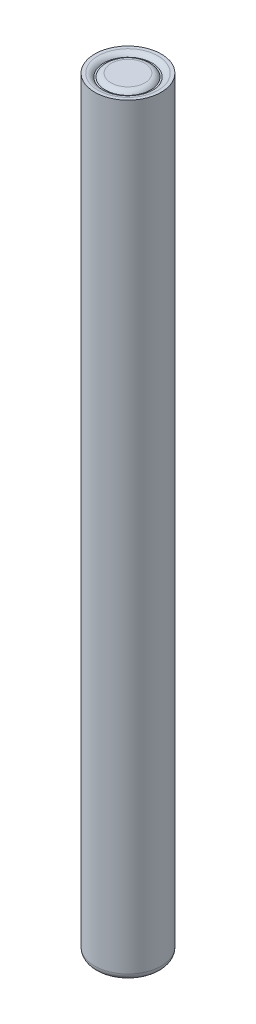
SolidWorks part; units mm, degrees
ref_plane "Front Plane" through (0, 0, 0) normal (0, 0, 1) x (1, 0, 0)
ref_plane "Top Plane" through (0, 0, 0) normal (0, 1, 0) x (1, 0, 0)
ref_plane "Right Plane" through (0, 0, 0) normal (1, 0, 0) x (0, 0, -1)
sketch "Sketch1" plane through (0, 0, 0) normal (0, 1, 0) x (1, 0, 0)
  circle A0 centre (0, 0) radius 5
  dimension "D1" = 10
extrude "Boss-Extrude1" add sketch "Sketch1" along normal blind 115
sketch "Sketch2" plane through (0, 0, 0) normal (0, -1, 0) x (1, 0, 0)
  circle A0 centre (0, 0) radius 1.5
  dimension "D1" = 3
extrude "Boss-Extrude2" add sketch "Sketch2" along normal blind 1
sketch "Sketch3" plane through (0, -1, 0) normal (0, -1, 0) x (1, 0, 0)
  circle A0 centre (0, 0) radius 0.5
  dimension "D1" = 1
extrude "Boss-Extrude3" add sketch "Sketch3" along normal blind 0.5
sketch "Sketch4" plane through (0, 115, 0) normal (0, 1, 0) x (1, 0, 0)
  circle A0 centre (0, 0) radius 3.6373
  circle A1 centre (0, 0) radius 3.4119
extrude "Cut-Extrude1" cut sketch "Sketch4" against normal blind 0.5
fillet "Fillet1" radius 1 2 edges at (0, 115, 3.6373) (0, 115, 3.4119)
fillet "Fillet2" radius 1 1 edges at (0, 0, 5)
fillet "Fillet6" radius 0.55 1 edges at (0, -1, -1.5)
fillet "Fillet7" radius 0.1 1 edges at (0, -1.5, -0.5)
